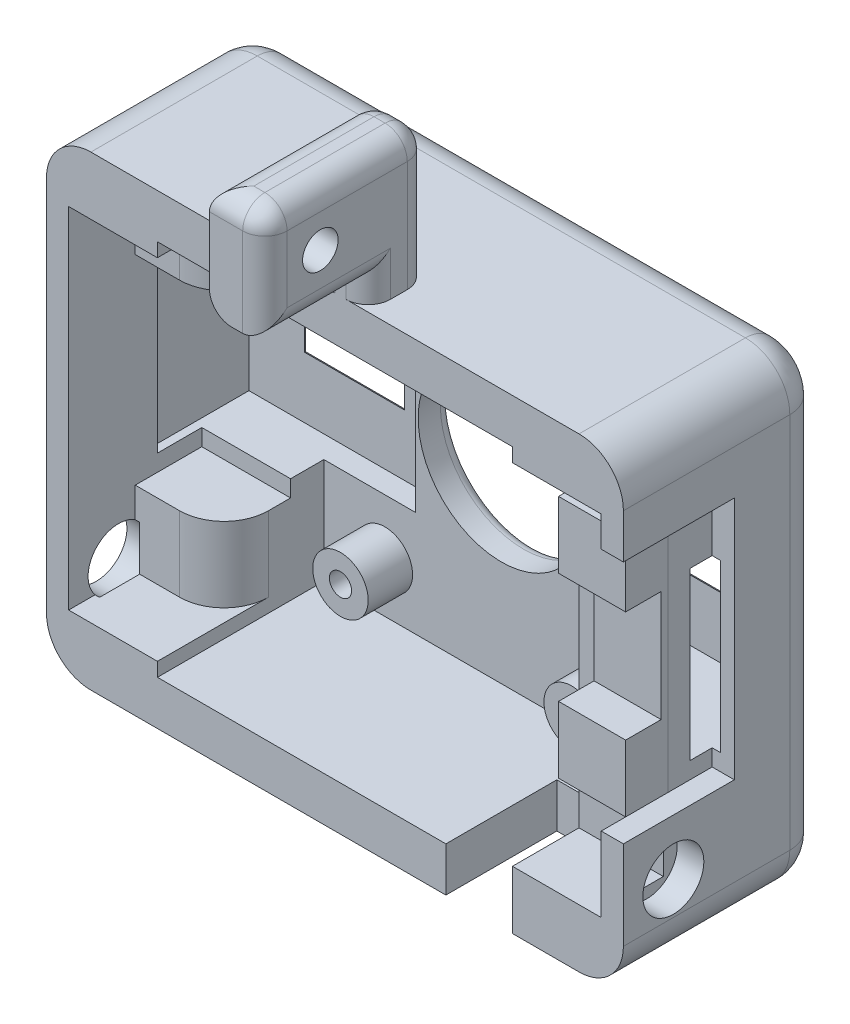
SolidWorks part; units mm, degrees
ref_plane "Front Plane" through (0, 0, 0) normal (0, 0, 1) x (1, 0, 0)
ref_plane "Top Plane" through (0, 0, 0) normal (0, 1, 0) x (1, 0, 0)
ref_plane "Right Plane" through (0, 0, 0) normal (1, 0, 0) x (0, 0, -1)
sketch "Sketch1" plane through (0, 0, 0) normal (0, 0, 1) x (1, 0, 0)
  line L1 (-26, 21) -> (26, 21)
  line L2 (-26, 21) -> (-26, -21)
  line L3 (-26, -21) -> (26, -21)
  line L4 (26, 21) -> (26, -21)
  line L5 (-26, 21) -> (26, -21) construction
  line L6 (-26, -21) -> (26, 21) construction
  point P0 (0, 0)
  dimension "D1" = 42
  dimension "D2" = 52
extrude "Boss-Extrude1" add sketch "Sketch1" along normal blind 10 contours L4 L3 L2 L1
sketch "Sketch2" plane through (0, 0, 10) normal (0, 0, 1) x (1, 0, 0)
  line L0 (-26, 21) -> (26, 21) construction
  line L1 (-24, 15.75) -> (24, 15.75)
  line L2 (-24, 15.75) -> (-24, -15.75)
  line L3 (-24, -15.75) -> (24, -15.75)
  line L4 (24, 15.75) -> (24, -15.75)
  line L5 (-24, 15.75) -> (24, -15.75) construction
  line L6 (-24, -15.75) -> (24, 15.75) construction
  line L7 (-26, -21) -> (26, -21) construction
  point P0 (0, 0)
  dimension "D1" = 5.25
  dimension "D2" = 48
  dimension "D3" = 5.25
extrude "Cut-Extrude1" cut sketch "Sketch2" against normal blind 6
sketch "Sketch6" plane through (0, 0, 0) normal (0, 0, -1) x (-1, 0, 0)
  line L1 (-26, 21) -> (26, 21)
  line L2 (-26, 21) -> (-26, -21)
  line L3 (-26, -21) -> (26, -21)
  line L4 (26, 21) -> (26, -21)
  line L5 (-26, 21) -> (26, -21) construction
  line L6 (-26, -21) -> (26, 21) construction
  point P0 (0, 0)
  dimension "D1" = 52
  dimension "D2" = 42
extrude "Boss-Extrude2" add sketch "Sketch6" along normal blind 8
sketch "Sketch5" plane through (0, 0, 4) normal (0, 0, 1) x (1, 0, 0)
  line L1 (-16, 17) -> (16, 17)
  line L2 (-16, 17) -> (-16, -17)
  line L3 (-16, -17) -> (16, -17)
  line L4 (16, 17) -> (16, -17)
  line L5 (-16, 17) -> (16, -17) construction
  line L6 (-16, -17) -> (16, 17) construction
  point P0 (0, 0)
  dimension "D1" = 34
  dimension "D2" = 32
extrude "Cut-Extrude5" cut sketch "Sketch5" against normal blind 9 and the other way through all
sketch "Sketch7" plane through (0, 0, -5) normal (0, 0, 1) x (1, 0, 0)
  circle A0 centre (0, 0) radius 7.5
  dimension "D1" = 15
extrude "Cut-Extrude4" cut sketch "Sketch7" against normal up to next
fillet "Fillet2" radius 1 1 edges at (-7.5, 0, -8)
fillet "Fillet3" radius 3 4 edges at (0, -21, -8) (-26, 0, -8) (26, 0, -8) (0, 21, -8)
fillet "Fillet4" radius 4 8 edges at (25.1213, 20.1213, -7.1213) (-25.1213, 20.1213, -7.1213) (-25.1213, -20.1213, -7.1213) (25.1213, -20.1213, -7.1213) (-26, 21, 2.5) (-26, -21, 2.5) (26, -21, 2.5) (26, 21, 2.5)
sketch "Sketch8" plane through (0, 0, 10) normal (0, 0, 1) x (1, 0, 0)
  line L0 (24, -15.75) -> (24, 15.75) construction
  line L5 (24, 13) -> (26, 13)
  line L6 (24, 13) -> (24, -9)
  line L7 (24, -9) -> (26, -9)
  line L8 (26, 13) -> (26, -9)
  line L9 (26, 17) -> (26, -17) construction
  line L10 (-22, 21) -> (22, 21) construction
  dimension "D1" = 22
  dimension "D2" = 8
extrude "Cut-Extrude6" cut sketch "Sketch8" against normal blind 10
sketch "Sketch11" plane through (0, 0, 4) normal (0, 0, 1) x (1, 0, 0)
  line L1 (24, 13) -> (17.954, 13)
  line L2 (24, 13) -> (24, -9)
  line L3 (24, -9) -> (17.954, -9)
  line L4 (17.954, 13) -> (17.954, -9)
  dimension "D1" = 6.046
  dimension "D2" = 22
extrude "Boss-Extrude9" add sketch "Sketch11" along normal blind 3.8 separate body
sketch "Sketch12" plane through (0, 0, 7.8) normal (0, 0, 1) x (1, 0, 0)
  line L0 (24, -9) -> (24, 13) construction
  line L1 (24, 7) -> (16.5, 7)
  line L2 (24, 7) -> (24, -3)
  line L3 (24, -3) -> (16.5, -3)
  line L4 (16.5, 7) -> (16.5, -3)
  line L5 (24, 13) -> (17.954, 13) construction
  line L7 (17.954, -9) -> (24, -9) construction
  dimension "D1" = 10
  dimension "D2" = 6
  dimension "D3" = 6
  dimension "D4" = 7.5
extrude "Cut-Extrude8" cut sketch "Sketch12" against normal blind 3.2
fillet "Fillet9" radius 4 1 edges at (-16, 0, 4)
sketch "Sketch13" plane through (26, 0, 0) normal (1, 0, 0) x (0, 0, -1)
  line L1 (-10, -9) -> (-10, -17) construction
  line L4 (-10, -17) -> (5, -17) construction
  circle A0 centre (-5.5, -14) radius 2.75
  dimension "D1" = 5.5
  dimension "D2" = 3
  dimension "D3" = 4.5
extrude "Cut-Extrude9" cut sketch "Sketch13" against normal blind 2.4
sketch "Sketch14" plane through (-26, 0, 0) normal (-1, 0, 0) x (0, 0, 1)
  line L1 (10, 17) -> (10, -17) construction
  line L2 (-5, -17) -> (10, -17) construction
  circle A0 centre (5.5, -14) radius 2.75
  dimension "D1" = 5.5
  dimension "D2" = 3
  dimension "D3" = 4.5
extrude "Cut-Extrude10" cut sketch "Sketch14" against normal blind 2.4
ref_plane "Plane2" through (0, 0, 2) normal (0, 0, -1) x (-1, 0, 0)
sketch "Sketch18" plane through (0, 0, 2) normal (0, 0, -1) x (-1, 0, 0)
  line L1 (-24.75, 7.5) -> (-7.75, 7.5)
  line L2 (-24.75, 7.5) -> (-24.75, -7.5)
  line L3 (-24.75, -7.5) -> (-7.75, -7.5)
  line L4 (-7.75, 7.5) -> (-7.75, -7.5)
  line L8 (7.75, 7.5) -> (24.75, 7.5)
  line L9 (7.75, 7.5) -> (7.75, -7.5)
  line L10 (7.75, -7.5) -> (24.75, -7.5)
  line L11 (24.75, 7.5) -> (24.75, -7.5)
  point P4 (-7.75, 0)
  point P5 (7.75, 0)
  dimension "D1" = 17
  dimension "D2" = 15
  dimension "D3" = 7.75
  dimension "D5" = 17
  dimension "D6" = 15
  dimension "D8" = 7.75
extrude "Cut-Extrude15" cut sketch "Sketch18" along normal blind 9
sketch "Sketch19" plane through (0, 0, -7) normal (0, 0, 1) x (1, 0, 0)
  line L1 (10.75, 2) -> (19.75, 2)
  line L2 (10.75, 2) -> (10.75, -2)
  line L3 (10.75, -2) -> (19.75, -2)
  line L4 (19.75, 2) -> (19.75, -2)
  line L7 (-19.75, 2) -> (-10.75, 2)
  line L8 (-19.75, 2) -> (-19.75, -2)
  line L9 (-19.75, -2) -> (-10.75, -2)
  line L10 (-10.75, 2) -> (-10.75, -2)
  line L12 (-7.75, 7.5) -> (-7.75, -7.5) construction
  line L13 (7.75, -7.5) -> (7.75, 7.5) construction
  point P6 (-10.75, 0)
  dimension "D1" = 9
  dimension "D2" = 4
  dimension "D3" = 3
  dimension "D5" = 9
  dimension "D6" = 4
  dimension "D7" = 3
extrude "Cut-Extrude16" cut sketch "Sketch19" against normal up to next (1 mm away)
sketch "Sketch21" plane through (0, 21, 0) normal (0, 1, 0) x (1, 0, 0)
  line L0 (-22, -10) -> (22, -10) construction
  line L1 (-2, -4.4799) -> (3, -4.4799)
  line L2 (-2, -4.4799) -> (-2, -10)
  line L3 (-2, -10) -> (3, -10)
  line L4 (3, -4.4799) -> (3, -10)
  line L5 (-26, -10) -> (-26, 5) construction
  dimension "D1" = 5
  dimension "D2" = 24
extrude "Boss-Extrude10" add sketch "Sketch21" along normal blind 2
sketch "Sketch27" plane through (0, 23, 0) normal (0, 1, 0) x (1, 0, 0)
  line L0 (-2, -4.4799) -> (-2, -10) construction
  line L1 (-2, -4.4799) -> (3, -4.4799)
  line L2 (-2, -4.4799) -> (-2, -19.3143)
  line L3 (-2, -19.3143) -> (3, -19.3143)
  line L4 (3, -4.4799) -> (3, -19.3143)
  line L5 (-2, -4.4799) -> (-2, -10) construction
  dimension "D1" = 14.8343
  dimension "D2" = 5
extrude "Boss-Extrude13" add sketch "Sketch27" along normal blind 10
sketch "Sketch28" plane through (-2, 0, 0) normal (-1, 0, 0) x (0, 0, 1)
  line L2 (19.3143, 33) -> (19.3143, 23) construction
  circle A0 centre (14.3143, 28) radius 1.6
  point P10 (19.3143, 28)
  dimension "D1" = 3.2
  dimension "D2" = 5
extrude "Cut-Extrude19" cut sketch "Sketch28" against normal through all
fillet "Fillet14" radius 2 11 edges at (0.5, 33, 4.4799) (3, 33, 11.8971) (0.5, 33, 19.3143) (-2, 33, 11.8971) (3, 27, 4.4799) (3, 28, 19.3143) (-2, 22, 10) (-2, 23, 14.6571) (-2, 27, 4.4799) (3, 23, 14.6571) (3, 22, 10)
fillet "Fillet13" radius 2 8 edges at (-19.75, 0, -8) (-10.75, 0, -8) (-15.25, -2, -8) (-15.25, 2, -8) (10.75, 0, -8) (19.75, 0, -8) (15.25, -2, -8) (15.25, 2, -8)
sketch "Sketch25" plane through (0, 0, -5) normal (0, 0, 1) x (1, 0, 0)
  line L0 (-10.5, 12.5) -> (10.5, 12.5) construction
  circle A0 centre (-10.5, 12.5) radius 2.5
  circle A1 centre (10.5, 12.5) radius 2.5
  circle A3 centre (-10.5, -12.5) radius 2.5
  circle A4 centre (10.3376, -12.5) radius 2.5
  point P4 (0, 12.5)
  dimension "D3" = 5
  dimension "D4" = 5
  dimension "D5" = 5
  dimension "D6" = 5
  dimension "D1" = 21
  dimension "D2" = 12.5
  dimension "D7" = 12.5
extrude "Boss-Extrude12" add sketch "Sketch25" along normal blind 4
sketch "Sketch26" plane through (0, 0, -1) normal (0, 0, 1) x (1, 0, 0)
  circle A0 centre (-10.5, 12.5) radius 1
  circle A1 centre (10.5, 12.5) radius 1
  circle A2 centre (-10.5, -12.5) radius 1
  circle A3 centre (10.3376, -12.5) radius 1
  dimension "D1" = 2
  dimension "D2" = 2
  dimension "D3" = 2
  dimension "D4" = 2
extrude "Cut-Extrude18" cut sketch "Sketch26" against normal blind 4
sketch "Sketch29" plane through (0, 0, 4) normal (0, 0, 1) x (1, 0, 0)
  line L0 (-16, 17) -> (-16, -17) construction
  line L1 (-24, 9) -> (-16, 9)
  line L2 (-24, 9) -> (-24, -9)
  line L3 (-24, -9) -> (-16, -9)
  line L4 (-16, 9) -> (-16, -9)
  point P6 (-16, 0)
  dimension "D1" = 8
  dimension "D2" = 18
extrude "Cut-Extrude20" cut sketch "Sketch29" against normal blind 6
sketch "Sketch30" plane through (0, 17, 0) normal (0, -1, 0) x (1, 0, 0)
  line L0 (22, -5) -> (22, 10) construction
  line L1 (-14, 4.0639) -> (14, 4.0639)
  line L2 (-14, 4.0639) -> (-14, -4.9361)
  line L3 (-14, -4.9361) -> (14, -4.9361)
  line L4 (14, 4.0639) -> (14, -4.9361)
  line L6 (-22, -5) -> (-22, 10) construction
  dimension "D1" = 8
  dimension "D2" = 8
  dimension "D3" = 9
extrude "Cut-Extrude21" cut sketch "Sketch30" against normal blind 2
fillet "Chamfer1" radius 1 2 edges at (14, 17, -0.4361) (-14, 17, -0.4361) profile chamfer
sketch "Sketch31" plane through (0, 0, 10) normal (0, 0, 1) x (1, 0, 0)
  line L0 (-22, -21) -> (22, -21) construction
  line L1 (16, -17) -> (10, -17)
  line L2 (16, -17) -> (16, -21)
  line L3 (16, -21) -> (10, -21)
  line L4 (10, -17) -> (10, -21)
  dimension "D1" = 6
  dimension "D2" = 4
extrude "Cut-Extrude22" cut sketch "Sketch31" against normal blind 10
